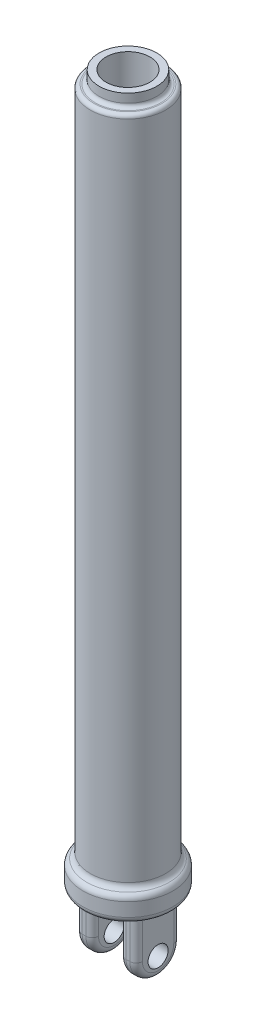
SolidWorks part; units mm, degrees
material "Plain Carbon Steel"
ref_plane "Front" through (0, 0, 0) normal (0, 0, 1) x (1, 0, 0)
ref_plane "Top" through (0, 0, 0) normal (0, 1, 0) x (1, 0, 0)
ref_plane "Right" through (0, 0, 0) normal (1, 0, 0) x (0, 0, -1)
sketch "Sketch1" plane through (0, 0, 0) normal (0, 0, 1) x (1, 0, 0)
  line L0 (0, 0) -> (0, 585) construction
  line L1 (-30, 552) -> (-30, 24.9774)
  line L2 (0, 565) -> (-23, 565) construction
  line L3 (0, 0) -> (-30.8239, 0)
  line L4 (-35.8239, 15.8911) -> (-35.8239, 5)
  line L5 (-27, 555) -> (-26, 555)
  line L6 (-23, 558) -> (-23, 565)
  line L7 (-17.5, 565) -> (-17.5, 40)
  line L8 (-17.5, 40) -> (0, 40)
  line L9 (-17.5, 565) -> (-23, 565)
  line L10 (0, 40) -> (0, 0)
  arc A1 (-30, 24.9774) -> (-32.9119, 20.4342) centre (-35, 24.9774) cw
  arc A2 (-35.8239, 15.8911) -> (-32.9119, 20.4342) centre (-30.8239, 15.8911) cw
  arc A3 (-30.8239, 0) -> (-35.8239, 5) centre (-30.8239, 5) cw
  arc A4 (-30, 552) -> (-27, 555) centre (-27, 552) cw
  arc A5 (-26, 555) -> (-23, 558) centre (-26, 558) ccw
  dimension "D2" = 5
  dimension "D3" = 5
  dimension "D5" = 3
  dimension "D8" = 565
  dimension "D1" = 585
  dimension "D4" = 30
  dimension "D6" = 10
  dimension "D7" = 1
  dimension "D9" = 525
  dimension "D10" = 35
revolve "Revolve1" add sketch "Sketch1" angle 360 about L10
sketch "Sketch2" plane through (0, 0, 0) normal (0, -1, 0) x (1, 0, 0)
  line L0 (0, 0) -> (0, 30.8239) construction
  line L1 (0, 0) -> (30.8239, 0) construction
  line L2 (-11, -17.5) -> (-24, 17.5) construction
  line L3 (11, 17.5) -> (24, 17.5)
  line L4 (11, 17.5) -> (11, -17.5)
  line L5 (11, -17.5) -> (24, -17.5)
  line L6 (24, 17.5) -> (24, -17.5)
  line L7 (11, 17.5) -> (24, -17.5) construction
  line L8 (11, -17.5) -> (24, 17.5) construction
  line L9 (-11, 17.5) -> (-24, -17.5) construction
  line L10 (-24, 17.5) -> (-24, -17.5)
  line L11 (-11, -17.5) -> (-24, -17.5)
  line L12 (-11, 17.5) -> (-11, -17.5)
  line L13 (-11, 17.5) -> (-24, 17.5)
  circle A0 centre (0, 0) radius 30.8239 construction
  point P6 (17.5, 0)
  point P16 (-17.5, 0)
  dimension "D1" = 35
  dimension "D2" = 48
  dimension "D3" = 22
extrude "Boss-Extrude1" add sketch "Sketch2" along normal blind 50
sketch "Sketch3" plane through (24, 0, 0) normal (1, 0, 0) x (0, 0, -1)
  line L0 (-17.5, -32.5) -> (-17.5, -50)
  line L1 (-17.5, -50) -> (17.5, -50)
  line L2 (17.5, -50) -> (17.5, -32.5)
  line L3 (-30.8239, 0) -> (30.8239, 0) construction
  arc A0 (-17.5, -32.5) -> (17.5, -32.5) centre (0, -32.5) ccw
  circle A2 centre (0, -35) radius 8
  line M2 (-17.5, 0) -> (-17.5, -50)
  line M3 (-17.5, -50) -> (17.5, -50)
  line M4 (17.5, -50) -> (17.5, 0)
  dimension "D1" = 16
  dimension "D2" = 35
extrude "Cut-Extrude1" cut sketch "Sketch3" against normal through all contours A0 M2 M3 | A0 L1 M4 | A2 region at (24, -46.0911, 13.5911) region at (24, -46.0911, -13.5911)
fillet "Fillet1" radius 5 12 edges at (24, -16.25, 17.5) (24, -16.25, -17.5) (11, -16.25, 17.5) (11, -16.25, -17.5) (-11, -16.25, -17.5) (-11, -16.25, 17.5) (-24, -16.25, 17.5) (-24, -16.25, -17.5) (24, -50, 0) (11, -50, 0) (-11, -50, 0) (-24, -50, 0)
ref_point "Point1"
